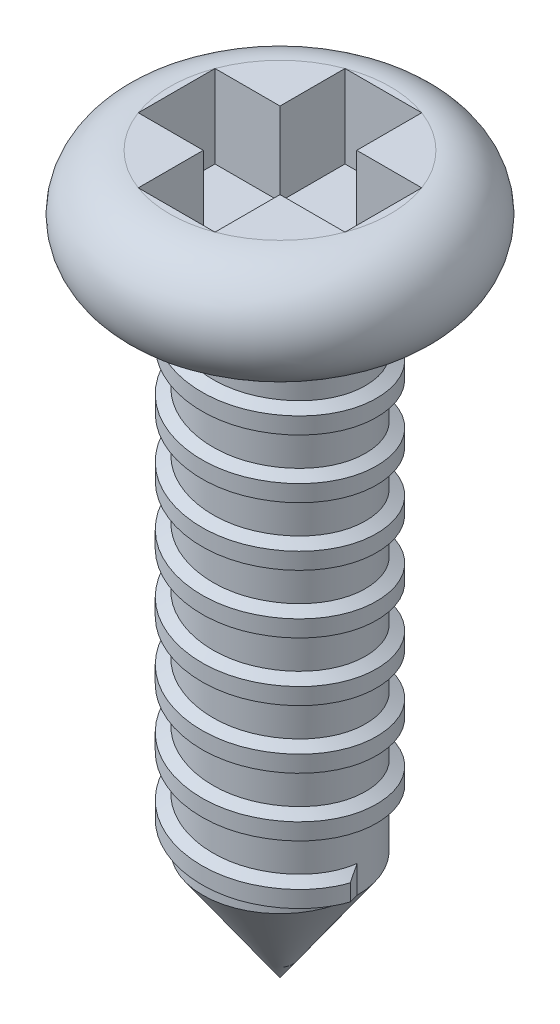
SolidWorks part; units mm, degrees
ref_plane "Front Plane" through (0, 0, 0) normal (0, 0, 1) x (1, 0, 0)
ref_plane "Top Plane" through (0, 0, 0) normal (0, 1, 0) x (1, 0, 0)
ref_plane "Right Plane" through (0, 0, 0) normal (1, 0, 0) x (0, 0, -1)
sketch "Screw Head Sketch" plane through (0, 0, 0) normal (0, 0, 1) x (1, 0, 0)
  line L0 (0, 1) -> (0, 0)
  line L1 (0, 0) -> (-1, 0)
  line L2 (0, 1) -> (-1, 1)
  arc A1 (-1, 1) -> (-1, 0) centre (-1, 0.5) ccw
  point P6 (-1.5, 0.5)
  dimension "D3" = 0.5
  dimension "D1" = 1
  dimension "D2" = 1.5
revolve "Screw Head Revolve" add sketch "Screw Head Sketch" angle 360 about L0
ref_plane "Screw Head Indent Plane" through (0, 1, 0) normal (0, 1, 0) x (1, 0, 0)
sketch "Screw Head Indent Sketch" plane through (0, 1, 0) normal (0, 1, 0) x (1, 0, 0)
  line L0 (0.3479, 0.3479) -> (0.9375, 0.3479)
  line L1 (-0.3479, 0.9375) -> (0.3479, 0.9375)
  line L2 (-0.3479, 0.9375) -> (-0.3479, 0.3479)
  line L3 (-0.3479, -0.9375) -> (0.3479, -0.9375)
  line L4 (0.3479, 0.9375) -> (0.3479, 0.3479)
  line L5 (-0.9375, 0.3479) -> (-0.3479, 0.3479)
  line L6 (-0.9375, 0.3479) -> (-0.9375, -0.3479)
  line L7 (-0.9375, -0.3479) -> (-0.3479, -0.3479)
  line L8 (0.9375, 0.3479) -> (0.9375, -0.3479)
  line L9 (-0.3479, -0.3479) -> (-0.3479, -0.9375)
  line L10 (0.3479, -0.3479) -> (0.9375, -0.3479)
  line L11 (0.3479, -0.3479) -> (0.3479, -0.9375)
  line L12 (0, 1) -> (0, -1) construction
  line L13 (-1, 0) -> (1, 0) construction
  circle A0 centre (0, 0) radius 1 construction
  point P19 (-0.9375, 0)
  point P20 (0, 0.9375)
extrude "Screw Head Indent" cut sketch "Screw Head Indent Sketch" against normal blind 0.75
sketch "Screw Body Sketch" plane through (0, 0, 0) normal (0, -1, 0) x (1, 0, 0)
  circle A0 centre (0, 0) radius 0.7
  dimension "D1" = 1.4
extrude "Screw Body" add sketch "Screw Body Sketch" along normal blind 4.5
sketch "Screw Tip Sketch" plane through (0, 0, 0) normal (0, 0, 1) x (1, 0, 0)
  line L0 (0, -4.5) -> (0, -5.5)
  line L1 (-0.7, -4.5) -> (0.7, -4.5) construction
  line L2 (0, -4.5) -> (0, 0) construction
  line L3 (0, -5.5) -> (0.7, -4.5)
  line L4 (0.7, -4.5) -> (0, -4.5)
  dimension "D1" = 1
revolve "Screw Tip" add sketch "Screw Tip Sketch" angle 360 about L0
ref_plane "Thread Plane" through (0, -0.125, 0) normal (0, -1, 0) x (-1, 0, 0)
sketch "Thread Circle Sketch" plane through (0, -0.125, 0) normal (0, -1, 0) x (-1, 0, 0)
  circle A0 centre (0, 0) radius 0.7 construction
  circle A1 centre (0, 0) radius 0.7
curve "Thread Helix/Spiral" pitch 0.5312 height 4.25 radius 0.7 left hand yes centre (0, -0.125, 0) axis (0, -1, 0) start towards (1, 0, 0)
sketch "Thread Profile" plane through (0, 0, 0) normal (0, 0, 1) x (1, 0, 0)
  line L0 (0.7, 0) -> (0.7, -0.25)
  line L1 (0.7, -4.5) -> (0.7, 0) construction
  line L5 (0.7, -0.25) -> (0.8, -0.2)
  line L6 (0.8, -0.2) -> (0.8, -0.05)
  line L7 (0.8, -0.05) -> (0.7, 0)
  line L8 (-1.1, -0.125) -> (1.1, -0.125) construction
  spline S0 degree 3 poles (0.7, -0.125) (0.7, -0.136) (0.6636, -0.1582) (0.5079, -0.1914) (0.1972, -0.2357) (-0.1972, -0.2799) (-0.5079, -0.3242) (-0.6636, -0.3574) (-0.7182, -0.3906) (-0.6636, -0.4238) (-0.5079, -0.457) (-0.1972, -0.5013) (0.1972, -0.5456) (0.5079, -0.5898) (0.6636, -0.623) (0.7182, -0.6562) (0.6636, -0.6895) (0.5079, -0.7227) (0.1972, -0.7669) (-0.1972, -0.8112) (-0.5079, -0.8555) (-0.6636, -0.8887) (-0.7182, -0.9219) (-0.6636, -0.9551) (-0.5079, -0.9883) (-0.1972, -1.0326) (0.1972, -1.0768) (0.5079, -1.1211) (0.6636, -1.1543) (0.7182, -1.1875) (0.6636, -1.2207) (0.5079, -1.2539) (0.1972, -1.2982) (-0.1972, -1.3424) (-0.5079, -1.3867) (-0.6636, -1.4199) (-0.7182, -1.4531) (-0.6636, -1.4863) (-0.5079, -1.5195) (-0.1972, -1.5638) (0.1972, -1.6081) (0.5079, -1.6523) (0.6636, -1.6855) (0.7182, -1.7188) (0.6636, -1.752) (0.5079, -1.7852) (0.1972, -1.8294) (-0.1972, -1.8737) (-0.5079, -1.918) (-0.6636, -1.9512) (-0.7182, -1.9844) (-0.6636, -2.0176) (-0.5079, -2.0508) (-0.1972, -2.0951) (0.1972, -2.1393) (0.5079, -2.1836) (0.6636, -2.2168) (0.7182, -2.25) (0.6636, -2.2832) (0.5079, -2.3164) (0.1972, -2.3607) (-0.1972, -2.4049) (-0.5079, -2.4492) (-0.6636, -2.4824) (-0.7182, -2.5156) (-0.6636, -2.5488) (-0.5079, -2.582) (-0.1972, -2.6263) (0.1972, -2.6706) (0.5079, -2.7148) (0.6636, -2.748) (0.7182, -2.7812) (0.6636, -2.8145) (0.5079, -2.8477) (0.1972, -2.8919) (-0.1972, -2.9362) (-0.5079, -2.9805) (-0.6636, -3.0137) (-0.7182, -3.0469) (-0.6636, -3.0801) (-0.5079, -3.1133) (-0.1972, -3.1576) (0.1972, -3.2018) (0.5079, -3.2461) (0.6636, -3.2793) (0.7182, -3.3125) (0.6636, -3.3457) (0.5079, -3.3789) (0.1972, -3.4232) (-0.1972, -3.4674) (-0.5079, -3.5117) (-0.6636, -3.5449) (-0.7182, -3.5781) (-0.6636, -3.6113) (-0.5079, -3.6445) (-0.1972, -3.6888) (0.1972, -3.7331) (0.5079, -3.7773) (0.6636, -3.8105) (0.7182, -3.8438) (0.6636, -3.877) (0.5079, -3.9102) (0.1972, -3.9544) (-0.1972, -3.9987) (-0.5079, -4.043) (-0.6636, -4.0762) (-0.7182, -4.1094) (-0.6636, -4.1426) (-0.5079, -4.1758) (-0.1972, -4.2201) (0.1972, -4.2643) (0.5079, -4.3086) (0.6636, -4.3418) (0.7, -4.364) (0.7, -4.375) knots 0 0 0 0 0.007813 0.015625 0.023438 0.039063 0.046875 0.054688 0.0625 0.070313 0.078125 0.085938 0.101563 0.109375 0.117188 0.125 0.132813 0.140625 0.148438 0.164063 0.171875 0.179688 0.1875 0.195313 0.203125 0.210938 0.226563 0.234375 0.242188 0.25 0.257813 0.265625 0.273438 0.289063 0.296875 0.304688 0.3125 0.320313 0.328125 0.335938 0.351563 0.359375 0.367188 0.375 0.382813 0.390625 0.398438 0.414063 0.421875 0.429688 0.4375 0.445313 0.453125 0.460938 0.476563 0.484375 0.492188 0.5 0.507813 0.515625 0.523438 0.539063 0.546875 0.554688 0.5625 0.570313 0.578125 0.585938 0.601563 0.609375 0.617188 0.625 0.632813 0.640625 0.648438 0.664063 0.671875 0.679688 0.6875 0.695313 0.703125 0.710938 0.726563 0.734375 0.742188 0.75 0.757813 0.765625 0.773438 0.789063 0.796875 0.804688 0.8125 0.820313 0.828125 0.835938 0.851563 0.859375 0.867188 0.875 0.882813 0.890625 0.898438 0.914062 0.921875 0.929688 0.9375 0.945312 0.953125 0.960938 0.976562 0.984375 0.992188 1 1 1 1 construction
  point P4 (0.7, -0.125)
  point P5 (0.8, -0.125)
  dimension "D1" = 0.1
  dimension "D2" = 0.25
  dimension "D3" = 0.15
sweep "Thread Sweep" add profiles "Thread Profile" path "Thread Helix/Spiral"
sketch "Upper Thread End Cut Profile" plane through (0, -0.125, 0) normal (0, -1, 0) x (-1, 0, 0)
  line L0 (-0.7, 0) -> (-0.8, 0.1732)
  line L1 (-0.8, 0.1732) -> (-0.8, 0)
  line L2 (-0.8, 0) -> (-0.7, 0) construction
  line L3 (-0.7, 0) -> (-0.8, 0)
  dimension "D1" = 60
  dimension "D2" = 0.1
  dimension "D3" = 0.2
  dimension "D4" = 0.1732
extrude "Upper Thread End Cut" cut sketch "Upper Thread End Cut Profile" against normal mid plane 0.25
ref_plane "Lower Thread End Cut Plane" through (0, -4.375, 0) normal (0, -1, 0) x (-1, 0, 0)
sketch "Lower Thread End Cut Profile" plane through (0, -4.375, 0) normal (0, -1, 0) x (-1, 0, 0)
  line L0 (-0.7, 0) -> (-0.8, 0)
  line L1 (-0.8, 0) -> (-0.8, -0.1732)
  line L2 (-0.8, -0.1732) -> (-0.7, 0)
  dimension "D1" = 60
  dimension "D2" = 0.1
  dimension "D3" = 0.2
  dimension "D4" = 0.1732
extrude "Lower Thread End Cut " cut sketch "Lower Thread End Cut Profile" against normal mid plane 0.3
